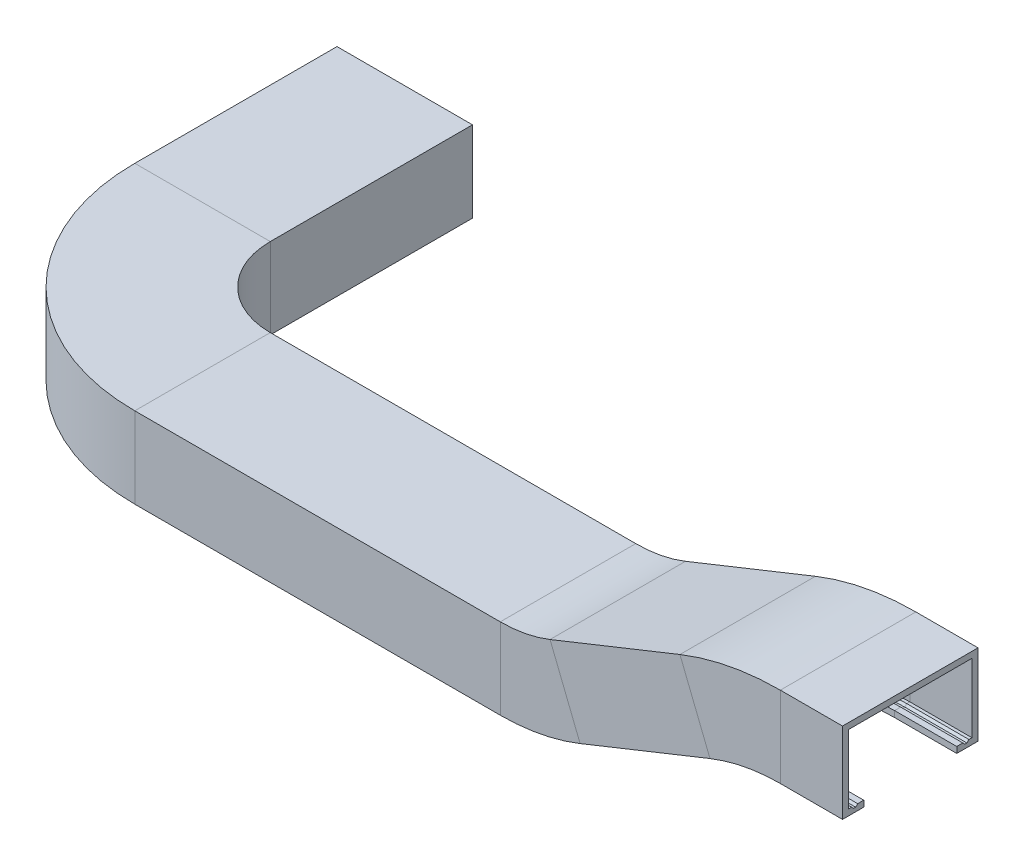
SolidWorks part; units mm, degrees
ref_plane "Front Plane" through (0, 0, 0) normal (0, 0, 1) x (1, 0, 0)
ref_plane "Top Plane" through (0, 0, 0) normal (0, 1, 0) x (1, 0, 0)
ref_plane "Right Plane" through (0, 0, 0) normal (1, 0, 0) x (0, 0, -1)
sketch "Sketch3" plane through (0, 0, 0) normal (1, 0, 0) x (0, 0, -1)
  line L0 (-380.9763, -129.5694) -> (-390.9763, -139.5694)
  line L1 (-395.9763, -96.5694) -> (154.0237, -96.5694) construction
  line L8 (-410.9763, -129.5694) -> (-425.9763, -129.5694)
  line L9 (-400.9763, -139.5694) -> (-410.9763, -129.5694)
  line L10 (-400.9763, -139.5694) -> (-390.9763, -139.5694)
  line L11 (-380.9763, -129.5694) -> (-350.9763, -129.5694)
  line L12 (-350.9763, -129.5694) -> (-350.9763, -159.5694)
  line L13 (-350.9763, -159.5694) -> (-455.9763, -159.5694)
  line L14 (-395.9763, -139.5694) -> (-395.9763, -96.5694) construction
  line L16 (154.0237, -96.5694) -> (154.0237, -139.5694) construction
  line L40 (-455.9763, -159.5694) -> (-455.9763, 240.4306)
  line L41 (-425.9763, 210.4306) -> (-425.9763, -129.5694)
  line L42 (-455.9763, 240.4306) -> (214.0237, 240.4306)
  line L43 (184.0237, 210.4306) -> (-425.9763, 210.4306)
  line L44 (184.0237, 210.4306) -> (184.0237, -129.5694)
  line L45 (214.0237, -159.5694) -> (214.0237, 240.4306)
  line L46 (139.0237, -129.5694) -> (109.0237, -129.5694)
  line L47 (109.0237, -129.5694) -> (109.0237, -159.5694)
  line L48 (139.0237, -129.5694) -> (149.0237, -139.5694)
  line L49 (159.0237, -139.5694) -> (169.0237, -129.5694)
  line L50 (109.0237, -159.5694) -> (214.0237, -159.5694)
  line L51 (159.0237, -139.5694) -> (149.0237, -139.5694)
  line L52 (169.0237, -129.5694) -> (184.0237, -129.5694)
  dimension "D1" = 109.0237
  dimension "D2" = 139.0237
  dimension "D3" = 149.0237
  dimension "D4" = 159.0237
  dimension "D5" = 184.0237
  dimension "D6" = 214.0237
  dimension "D7" = 350.9763
  dimension "D8" = 210.4306
  dimension "D9" = 240.4306
  dimension "D10" = 96.5694
  dimension "D11" = 129.5694
ref_plane "Plane1" through (0, -96.5694, 0) normal (0, 1, 0) x (1, 0, 0)
sketch "Sketch4" plane through (0, -96.5694, 0) normal (0, 1, 0) x (1, 0, 0)
  line L0 (0, -395.9763) -> (-1000, -395.9763)
  line L1 (-2000, 604.0237) -> (-2000, 1604.0237)
  line L2 (0, 154.0237) -> (-1000, 154.0237)
  line L3 (-1450, 604.0237) -> (-1450, 1604.0237)
  arc A0 (-1000, -395.9763) -> (-2000, 604.0237) centre (-1000, 604.0237) cw
  arc A1 (-1000, 154.0237) -> (-1450, 604.0237) centre (-1000, 604.0237) cw
  point P6 (-2000, -395.9763)
  dimension "D3" = 1000
  dimension "D1" = 2000
  dimension "D2" = 2000
  dimension "D4" = 550
ref_plane "Plane2" through (0, -159.5694, 0) normal (0, 1, 0) x (1, 0, 0)
sweep "Sweep15" add profiles "Sketch3" path "Sketch4"
ref_plane "Plane3" through (0, 0, 395.9763) normal (0, 0, -1) x (-1, 0, 0)
sketch "Sketch20" plane through (0, 0, 395.9763) normal (0, 0, -1) x (-1, 0, 0)
  line L0 (0, -96.5694) -> (-807.4176, -96.5694)
  line L1 (-1178.8083, -25.0461) -> (-1821.1917, 231.9073)
  line L2 (-2192.5824, 303.4306) -> (-2500, 303.4306)
  arc A0 (-1821.1917, 231.9073) -> (-2192.5824, 303.4306) centre (-2192.5824, -696.5694) ccw
  arc A1 (-807.4176, -96.5694) -> (-1178.8083, -25.0461) centre (-807.4176, 903.4306) cw
  point P7 (-2000, 303.4306)
  point P10 (-1000, -96.5694)
  dimension "D4" = 1000
  dimension "D1" = 1000
  dimension "D2" = 1000
  dimension "D3" = 500
  dimension "D5" = 400
sweep "Sweep18" add profiles "Sketch3<10>" path "Sketch20"
sketch "Sketch3<10>" plane through (0, 0, 0) normal (1, 0, 0) x (0, 0, -1) same geometry as "Sketch3"
